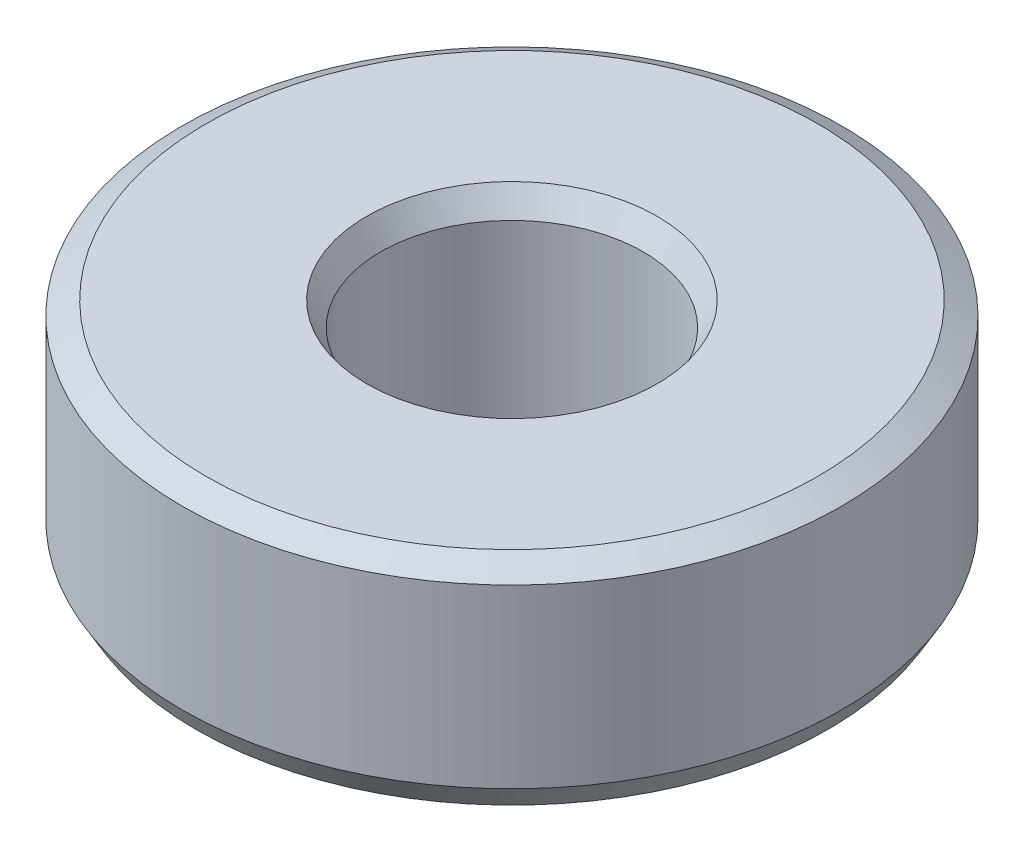
SolidWorks part; units mm, degrees
ref_plane "Front Plane" through (0, 0, 0) normal (0, 0, 1) x (1, 0, 0)
ref_plane "Top Plane" through (0, 0, 0) normal (0, 1, 0) x (1, 0, 0)
ref_plane "Right Plane" through (0, 0, 0) normal (1, 0, 0) x (0, 0, -1)
sketch "Sketch1" plane through (0, 0, 0) normal (0, 1, 0) x (1, 0, 0)
  circle A0 centre (0, 0) radius 37.5
  dimension "SLEEVE_OD" = 75
extrude "Boss-Extrude1" add sketch "Sketch1" along normal blind 24.3681
sketch "Sketch2" plane through (0, 0, 0) normal (0, 1, 0) x (1, 0, 0)
  circle A0 centre (0, 0) radius 14.9507
  dimension "BORE_D" = 29.9014
extrude "Cut-Extrude1" cut sketch "Sketch2" along normal through all
chamfer "Chamfer1" distance 1.5708 angle 60 4 edges at (0, 24.3681, 14.9507) (0, 0, 14.9507) (0, 0, 37.5) (0, 24.3681, 37.5) first distance on face at (0, 24.3681, 14.9507) first distance on face at (0, 0, 14.9507) first distance on face at (0, 24.3681, 37.5)
